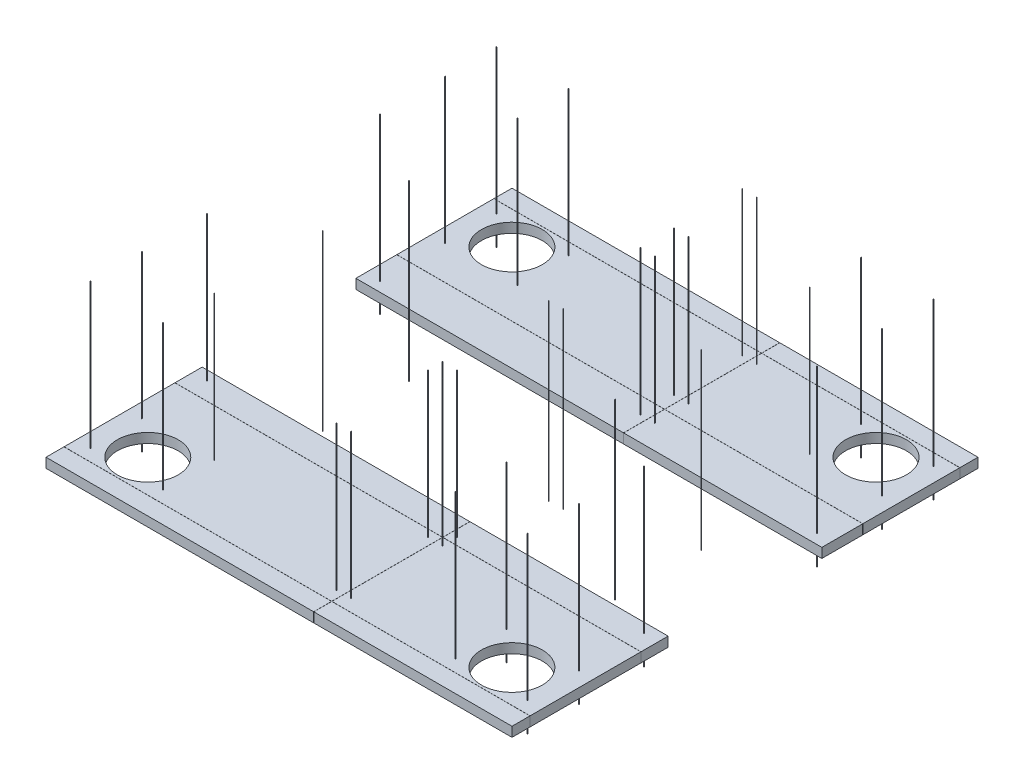
SolidWorks part; units mm, degrees
ref_plane "Front" through (0, 0, 0) normal (0, 0, 1) x (1, 0, 0)
ref_plane "Top" through (0, 0, 0) normal (0, 1, 0) x (1, 0, 0)
ref_plane "Right" through (0, 0, 0) normal (1, 0, 0) x (0, 0, -1)
sketch "Sketch1" plane through (0, 0, 0) normal (0, 1, 0) x (1, 0, 0)
  line L1 (-2454.275, 2454.275) -> (2454.275, 2454.275)
  line L2 (-2454.275, 2454.275) -> (-2454.275, -2454.275)
  line L3 (-2454.275, -2454.275) -> (2454.275, -2454.275)
  line L4 (2454.275, 2454.275) -> (2454.275, -2454.275)
  line L5 (-2454.275, 2454.275) -> (2454.275, -2454.275) construction
  line L6 (-2454.275, -2454.275) -> (2454.275, 2454.275) construction
  point P0 (0, 0)
  dimension "D1" = 4908.55
  dimension "D2" = 4908.55
extrude "Boss-Extrude1" add sketch "Sketch1" along normal blind 101.6
sketch "Sketch2" plane through (0, 101.6, 0) normal (0, 1, 0) x (1, 0, 0)
  line L0 (-2454.275, 2454.275) -> (-2454.275, -2454.275) construction
  line L1 (2454.275, -809.625) -> (-2454.275, -809.625)
  line L2 (2454.275, -809.625) -> (2454.275, 809.625)
  line L3 (2454.275, 809.625) -> (-2454.275, 809.625)
  line L4 (-2454.275, -809.625) -> (-2454.275, 809.625)
  line L5 (2454.275, -809.625) -> (-2454.275, 809.625) construction
  line L6 (2454.275, 809.625) -> (-2454.275, -809.625) construction
  point P0 (0, 0)
  dimension "D1" = 1619.25
extrude "Cut-Extrude1" cut sketch "Sketch2" against normal through all
sketch "Sketch4" plane through (0, 101.6, 0) normal (0, 1, 0) x (1, 0, 0)
  line L0 (-2454.275, -2263.775) -> (2454.275, -2263.775)
  line L3 (-2454.275, -2454.275) -> (2454.275, -2454.275) construction
  line L4 (-2454.275, -1095.375) -> (2454.275, -1095.375)
  line L5 (-2454.275, -809.625) -> (-2454.275, -2454.275) construction
  line L6 (-2454.275, -809.625) -> (2454.275, -809.625) construction
  line L7 (-2454.275, 2263.775) -> (2454.275, 2263.775)
  line L10 (-2454.275, 1241.425) -> (2454.275, 1241.425)
  line L11 (-2454.275, 2454.275) -> (-2454.275, 809.625) construction
  line L12 (2454.275, 809.625) -> (2454.275, 2454.275) construction
  line L13 (2454.275, 2454.275) -> (-2454.275, 2454.275) construction
  line L14 (2454.275, 809.625) -> (-2454.275, 809.625) construction
  line L15 (-2454.275, -1095.375) -> (-2454.275, -2263.775) construction
  line L16 (2454.275, -1095.375) -> (2454.275, -2263.775) construction
  line L17 (2454.275, 1241.425) -> (2454.275, 2263.775) construction
  line L18 (-2454.275, 1241.425) -> (-2454.275, 2263.775) construction
  line L19 (2454.275, -2454.275) -> (2454.275, -809.625) construction
  dimension "D1" = 190.5
  dimension "D2" = 1168.4
  dimension "D3" = 285.75
  dimension "D4" = 190.5
  dimension "D5" = 1022.35
  dimension "D6" = 431.8
extrude "Cut-Extrude-Thin1" cut sketch "Sketch4" against normal through all thin thin type one direction wall 1.27
sketch "Sketch5" plane through (0, 101.6, 0) normal (0, 1, 0) x (1, 0, 0)
  line L0 (365.125, -2454.275) -> (365.125, 2454.275)
  line L1 (-2454.275, -2454.275) -> (2454.275, -2454.275) construction
  line L2 (2454.275, 2454.275) -> (-2454.275, 2454.275) construction
  line L3 (2454.275, -2263.775) -> (2454.275, -1096.645) construction
  line L4 (-2454.275, -1096.645) -> (-2454.275, -2263.775) construction
  dimension "D1" = 2089.15
  dimension "D2" = 2819.4
extrude "Cut-Extrude-Thin2" cut sketch "Sketch5" against normal through all and the other way through all thin thin type one direction wall 1.27
sketch "Sketch8" plane through (0, 101.6, 0) normal (0, 1, 0) x (1, 0, 0)
  line L0 (-974.0807, 502.3386) -> (-974.0807, 1597.0052) construction
sketch "Sketch6" plane through (0, 101.6, 0) normal (0, 1, 0) x (1, 0, 0)
  line L0 (1917.7, 1916.43) -> (1917.7, 2262.505) construction
  line L1 (-1917.7, 1916.43) -> (1917.7, 1916.43) construction
  line L2 (-1917.7, 1916.43) -> (-1917.7, -1918.97) construction
  line L3 (-1917.7, -1918.97) -> (1917.7, -1918.97) construction
  line L4 (1917.7, 1916.43) -> (1917.7, -1918.97) construction
  line L5 (-1917.7, -1918.97) -> (-1917.7, -2265.045) construction
  line L6 (-2454.275, -2265.045) -> (365.125, -2265.045) construction
  line L7 (366.395, 2262.505) -> (2454.275, 2262.505) construction
  line L9 (2454.275, 1241.425) -> (2454.275, 2262.505) construction
  line L11 (-2454.275, -1096.645) -> (-2454.275, -2263.775) construction
  circle A0 centre (1917.7, 1916.43) radius 320.675
  circle A1 centre (-1917.7, 1916.43) radius 320.675
  circle A2 centre (-1917.7, -1918.97) radius 320.675
  circle A3 centre (1917.7, -1918.97) radius 320.675
  dimension "D1" = 641.35
  dimension "D3" = 215.9
  dimension "D4" = 215.9
  dimension "D2" = 25.4
extrude "DUCT HOLES" cut sketch "Sketch6" against normal through all
sketch "Sketch7" plane through (0, 101.6, 0) normal (0, 1, 0) x (1, 0, 0)
  line L0 (-1539.875, 2301.875) -> (-346.075, 2301.875) construction
  line L1 (-1539.875, 2301.875) -> (-2454.275, 2301.875) construction
  line L2 (-2454.275, 2454.275) -> (-2454.275, 2263.775) construction
  line L3 (365.125, 2454.275) -> (-2454.275, 2454.275) construction
  line L4 (-346.075, 2301.875) -> (365.125, 2301.875) construction
  line L5 (365.125, 2263.775) -> (365.125, 2454.275) construction
  line L6 (1539.875, 1597.025) -> (1539.875, 1063.625) construction
  line L7 (365.125, 2301.875) -> (974.725, 2301.875) construction
  line L8 (974.725, 2301.875) -> (1539.875, 2301.875) construction
  line L9 (1539.875, 2301.875) -> (2454.275, 2301.875) construction
  line L10 (2454.275, 2263.775) -> (2454.275, 2454.275) construction
  line L11 (366.395, 2263.775) -> (366.395, 2454.275) construction
  line L12 (2454.275, 1597.025) -> (-2454.275, 1597.025) construction
  line L13 (2454.275, 1241.425) -> (2454.275, 2262.505) construction
  line L14 (-2454.275, 2262.505) -> (-2454.275, 1241.425) construction
  line L15 (1539.875, 2301.875) -> (1539.875, 1597.025) construction
  line L16 (-2454.275, 1241.425) -> (365.125, 1241.425) construction
  line L17 (-346.075, 2301.875) -> (-346.075, 1597.025) construction
  line L18 (974.725, 2301.875) -> (974.725, 1597.025) construction
  line L19 (-2454.275, 2136.775) -> (2454.275, 2136.775) construction
  line L20 (-2454.275, 2263.775) -> (365.125, 2263.775) construction
  line L21 (-1539.875, 2301.875) -> (-1539.875, 2136.775) construction
  line L22 (-2454.275, 1063.625) -> (2454.275, 1063.625) construction
  line L23 (-2454.275, 1240.155) -> (-2454.275, 809.625) construction
  line L24 (2454.275, 809.625) -> (2454.275, 1240.155) construction
  line L25 (365.125, 809.625) -> (-2454.275, 809.625) construction
  line L26 (-1539.875, 1063.625) -> (-1539.875, 1597.025) construction
  line L27 (-346.075, 1597.025) -> (-346.075, 1063.625) construction
  line L28 (-2107.4102, -2022.1425) -> (-2107.4102, -819.4758) construction
  line L29 (-1539.875, 1285.875) -> (1539.875, 1285.875) construction
  line L30 (-2301.875, 1597.025) -> (-2301.875, 1063.625) construction
  line L31 (2301.875, 1597.025) -> (2301.875, 1063.625) construction
  line L32 (-2454.275, 1240.155) -> (365.125, 1240.155) construction
  line L33 (441.325, 1063.625) -> (288.925, 1063.625) construction
  line L34 (441.325, 1063.625) -> (441.325, 1416.685) construction
  line L35 (441.325, 1416.685) -> (288.925, 1416.685) construction
  line L36 (288.925, 1063.625) -> (288.925, 1416.685) construction
  line L37 (-2454.275, 1240.155) -> (365.125, 1240.155) construction
  line L38 (365.125, 809.625) -> (365.125, 1240.155) construction
  line L39 (365.125, 809.625) -> (365.125, 1240.155) construction
  line L40 (440.6472, 1241.425) -> (440.6472, 1063.625) construction
  line L41 (288.925, -1172.845) -> (441.325, -1172.845) construction
  line L42 (288.925, -1172.845) -> (288.925, -1020.445) construction
  line L43 (288.925, -1020.445) -> (441.325, -1020.445) construction
  line L44 (441.325, -1172.845) -> (441.325, -1020.445) construction
  line L45 (366.395, 1241.425) -> (2454.275, 1241.425) construction
  line L46 (1539.875, 1063.625) -> (1539.875, -2454.275) construction
  line L47 (366.395, -2454.275) -> (2454.275, -2454.275) construction
  line L48 (-2454.275, -1096.645) -> (365.125, -1096.645) construction
  line L49 (-2454.275, -1096.645) -> (365.125, -1096.645) construction
  line L50 (-2301.875, 1063.625) -> (-2301.875, 911.225) construction
  line L51 (-2301.875, 911.225) -> (2301.875, 911.225) construction
  line L52 (2301.875, 911.225) -> (2301.875, 1063.625) construction
  line L53 (-1539.875, 1063.625) -> (-1539.875, -2454.275) construction
  line L54 (-2454.275, -2454.275) -> (365.125, -2454.275) construction
  line L55 (1539.875, 454.025) -> (-1539.875, 454.025) construction
  line L56 (288.925, 1063.625) -> (288.925, -2454.275) construction
  line L57 (441.325, 1063.625) -> (441.325, -2454.275) construction
  line L58 (-346.075, 1063.625) -> (-346.075, -2454.275) construction
  line L59 (441.325, 98.425) -> (288.925, 98.425) construction
  line L60 (441.325, 1063.625) -> (441.325, 2301.875) construction
  line L61 (288.925, 1063.625) -> (288.925, 2301.875) construction
  circle A0 centre (-1539.875, 2301.875) radius 3.175 construction
  circle A4 centre (1539.875, 1597.025) radius 3.175
  circle A5 centre (-1539.875, 1597.025) radius 3.175
  circle A6 centre (441.325, 1063.625) radius 3.175
  circle A7 centre (-346.075, 1597.025) radius 3.175 construction
  circle A8 centre (974.725, 1597.025) radius 3.175 construction
  circle A9 centre (-346.075, 2136.775) radius 3.175 construction
  circle A10 centre (-1539.875, 2136.775) radius 3.175
  circle A11 centre (974.725, 2136.775) radius 3.175 construction
  circle A12 centre (1539.875, 2136.775) radius 3.175
  circle A13 centre (-346.075, 1063.625) radius 3.175 construction
  circle A14 centre (-1539.875, 1063.625) radius 3.175 construction
  circle A15 centre (1539.875, 1063.625) radius 3.175 construction
  circle A16 centre (-2301.875, 1597.025) radius 3.175
  circle A17 centre (2301.875, 1597.025) radius 3.175
  circle A18 centre (-2301.875, 2136.775) radius 3.175
  circle A19 centre (2301.875, 2136.775) radius 3.175
  circle A20 centre (219.075, 2301.875) radius 3.175 construction
  circle A21 centre (658.495, 2301.875) radius 3.175 construction
  circle A22 centre (1539.875, 2301.875) radius 3.175 construction
  circle A23 centre (-650.875, 2301.875) radius 3.175 construction
  circle A24 centre (-1539.875, 1285.875) radius 3.175 construction
  circle A25 centre (1539.875, 1285.875) radius 3.175 construction
  circle A26 centre (-2301.875, 1063.625) radius 3.175 construction
  circle A27 centre (2301.875, 1063.625) radius 3.175 construction
  circle A28 centre (288.925, 1416.685) radius 3.175
  circle A29 centre (441.325, 1416.685) radius 3.175
  circle A30 centre (288.925, 1063.625) radius 3.175
  circle A31 centre (441.325, -1020.445) radius 3.175
  circle A32 centre (288.925, -1020.445) radius 3.175
  circle A33 centre (288.925, -1172.845) radius 3.175
  circle A34 centre (441.325, -1172.845) radius 3.175
  circle A35 centre (-2301.875, 911.225) radius 3.175
  circle A36 centre (2301.875, 911.225) radius 3.175
  circle A37 centre (1539.875, 454.025) radius 3.175
  circle A38 centre (-1539.875, 454.025) radius 3.175
  circle A41 centre (-346.075, 454.025) radius 3.175 construction
  circle A43 centre (441.325, 98.425) radius 3.175
  circle A44 centre (288.925, 98.425) radius 3.175
  circle A45 centre (288.925, 2136.775) radius 3.175
  circle A47 centre (441.325, 2136.775) radius 3.175
  point P107 (288.925, -1096.645)
  dimension "D1" = 6.35
  dimension "D5" = 609.6
  dimension "D7" = 355.6
  dimension "D11" = 152.4
  dimension "D14" = 152.4
  dimension "D19" = 889
  dimension "D20" = 914.4
  dimension "D21" = 1168.4
  dimension "D25" = 457.2
  dimension "D26" = 355.6
  dimension "D2" = 152.4
  dimension "D3" = 914.4
  dimension "D4" = 711.2
  dimension "D6" = 914.4
  dimension "D8" = 914.4
  dimension "D9" = 127
  dimension "D10" = 152.4
  dimension "D12" = 254
  dimension "D13" = 152.4
  dimension "D15" = 152.4
  dimension "D16" = 146.05
  dimension "D17" = 292.1
  dimension "D18" = 914.4
  dimension "D22" = 3079.75
  dimension "D23" = 152.4
  dimension "D24" = 152.4
extrude "UNISTRUT STUD LAYOUT" add sketch "Sketch7" along normal blind 1524 and the other way blind 304.8 separate body
mirror "Mirror3" about plane through (0, 0, 0) normal (0, 0, 1) of bodies 251 222 252 271 272 286 302 301 306 305 316 315 320 321 240 223 227 214 238 225 241 215 226 224 228 217 244 229 216 275 276 277 281 283 287 288 293 291 292 309
